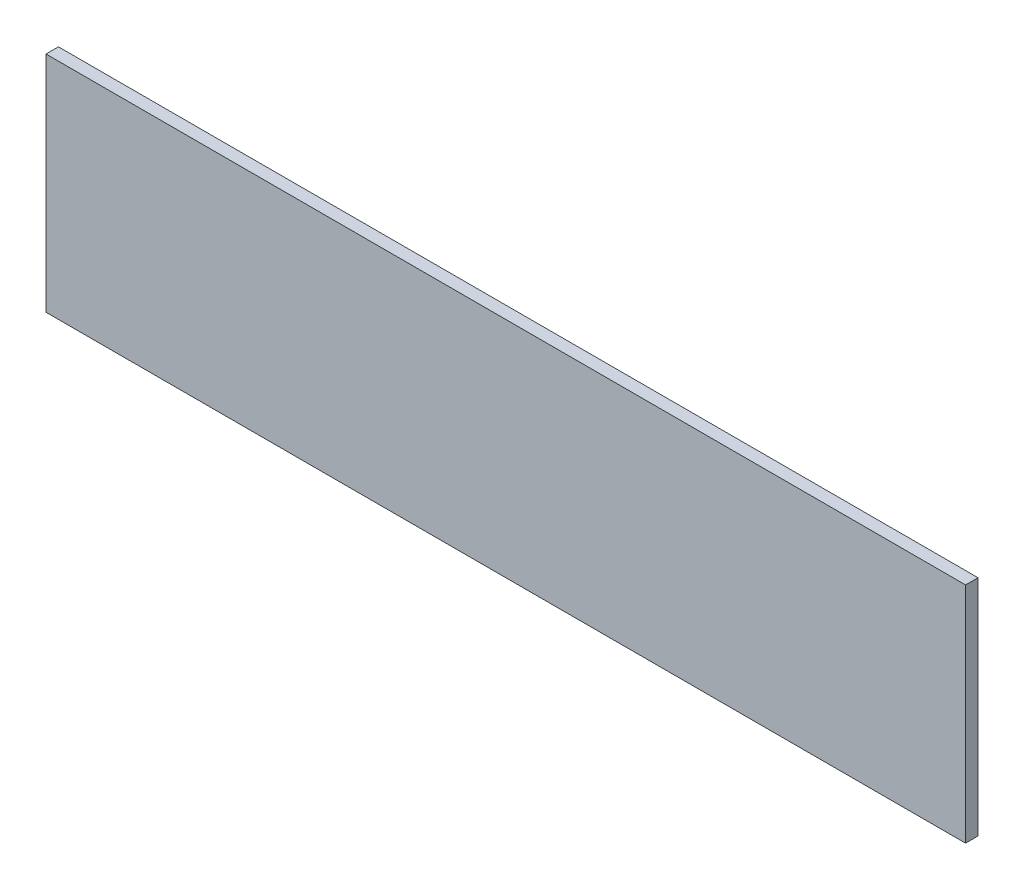
SolidWorks part; units mm, degrees
ref_plane "Front Plane" through (0, 0, 0) normal (0, 0, 1) x (1, 0, 0)
ref_plane "Top Plane" through (0, 0, 0) normal (0, 1, 0) x (1, 0, 0)
ref_plane "Right Plane" through (0, 0, 0) normal (1, 0, 0) x (0, 0, -1)
sketch "Sketch1" plane through (0, 0, 0) normal (0, 0, 1) x (1, 0, 0)
  line L1 (-185, 45) -> (185, 45)
  line L2 (-185, 45) -> (-185, -45)
  line L3 (-185, -45) -> (185, -45)
  line L4 (185, 45) -> (185, -45)
  line L5 (-185, 45) -> (185, -45) construction
  line L6 (-185, -45) -> (185, 45) construction
  point P0 (0, 0)
  dimension "D1" = 370
  dimension "D2" = 90
extrude "Boss-Extrude1" add sketch "Sketch1" along normal blind 5
